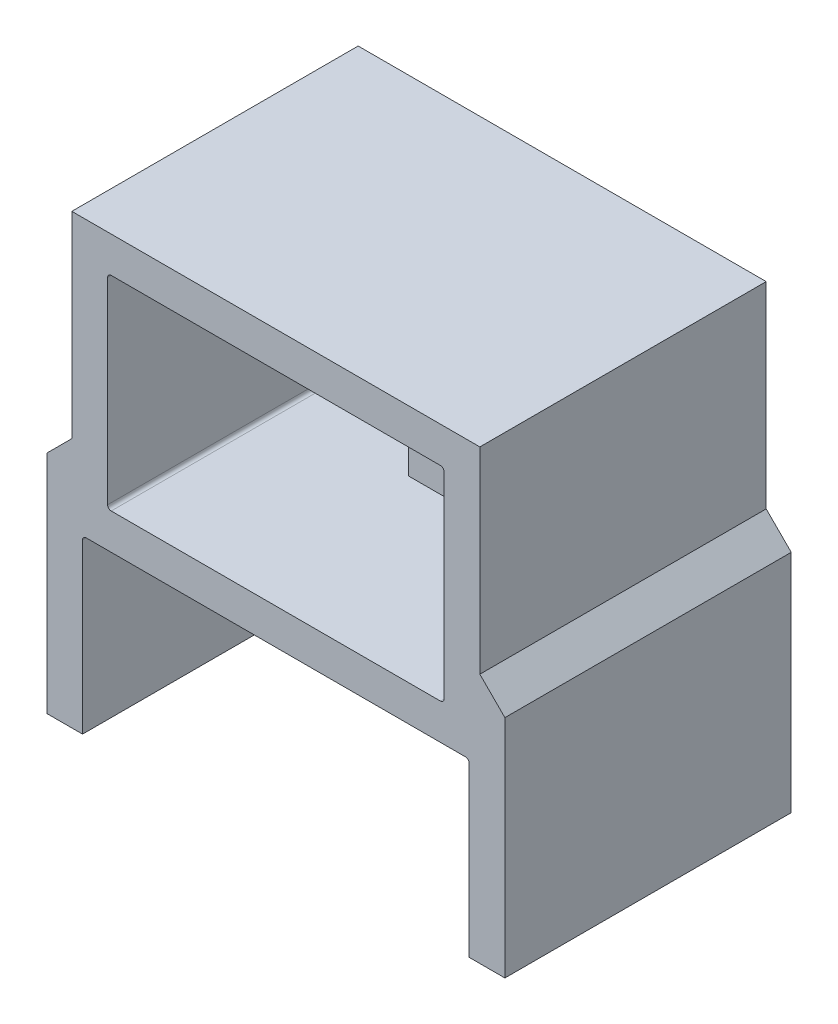
SolidWorks part; units mm, degrees
ref_plane "正面" through (0, 0, 0) normal (0, 0, 1) x (1, 0, 0)
ref_plane "平面" through (0, 0, 0) normal (0, 1, 0) x (1, 0, 0)
ref_plane "右側面" through (0, 0, 0) normal (1, 0, 0) x (0, 0, -1)
sketch "ｽｹｯﾁ1" plane through (0, 0, 0) normal (0, 0, 1) x (1, 0, 0)
  line L0 (0, 6.3) -> (0, 0)
  line L1 (0, 0) -> (12.8, 0)
  line L2 (12.8, 0) -> (12.8, 6.3)
  line L3 (12.8, 6.3) -> (12.1, 6.3)
  line L4 (12.1, 6.3) -> (12.1, 12.5)
  line L5 (12.1, 12.5) -> (0.7, 12.5)
  line L6 (0.7, 12.5) -> (0.7, 6.3)
  line L7 (0.7, 6.3) -> (0, 6.3)
  line L8 (6.4, 0) -> (6.4, -50000) construction
  point P11 (6.4, 0)
  point P12 (6.4, 12.5)
  dimension "D1" = 11.4
  dimension "D2" = 12.8
  dimension "D3" = 12.5
  dimension "D4" = 6.2
extrude "ﾎﾞｽ - 押し出し1" add sketch "ｽｹｯﾁ1" along normal blind 8
chamfer "面取り1" distance 0.7 angle 45 2 edges at (0.7, 6.3, 4) (12.1, 6.3, 4)
sketch "ｽｹｯﾁ3" plane through (0, 0, 8) normal (0, 0, 1) x (1, 0, 0)
  line L0 (12.8, 0) -> (12.8, 6.3) construction
  line L1 (1, 0) -> (11.8, 0)
  line L2 (1, 0) -> (1, 4.8)
  line L3 (1, 4.8) -> (11.8, 4.8)
  line L4 (11.8, 0) -> (11.8, 4.8)
  line L5 (0, 6.3) -> (0, 0) construction
  line L6 (12.1, 12.5) -> (0.7, 12.5) construction
  line L7 (1.7, 11.5) -> (11.1, 11.5)
  line L8 (1.7, 11.5) -> (1.7, 5.8)
  line L9 (1.7, 5.8) -> (11.1, 5.8)
  line L10 (11.1, 11.5) -> (11.1, 5.8)
  line L11 (1.7, 11.5) -> (11.1, 5.8) construction
  line L12 (1.7, 5.8) -> (11.1, 11.5) construction
  line L13 (12.1, 7) -> (12.1, 12.5) construction
  line L14 (0.7, 12.5) -> (0.7, 7) construction
  line L15 (0, 0) -> (12.8, 0) construction
  point P8 (6.4, 8.65)
  dimension "D1" = 1
  dimension "D2" = 1
  dimension "D3" = 1
  dimension "D4" = 1
  dimension "D5" = 1
  dimension "D6" = 1
  dimension "D7" = 5.7
extrude "ｶｯﾄ - 押し出し1" cut sketch "ｽｹｯﾁ3" against normal blind 7.2
fillet "ﾌｨﾚｯﾄ1" radius 0.1 6 edges at (11.8, 4.8, 4.4) (1, 4.8, 4.4) (1.7, 5.8, 4.4) (11.1, 5.8, 4.4) (11.1, 11.5, 4.4) (1.7, 11.5, 4.4)
sketch "ｽｹｯﾁ4" plane through (0, 4.8, 0) normal (0, -1, 0) x (1, 0, 0)
  line L1 (11.8, 0.8) -> (6.1, 0.8)
  line L2 (11.8, 0.8) -> (11.8, 2)
  line L3 (11.8, 2) -> (6.1, 2)
  line L4 (6.1, 0.8) -> (6.1, 2)
  dimension "D1" = 5.7
  dimension "D2" = 1.2
extrude "ｶｯﾄ - 押し出し2" cut sketch "ｽｹｯﾁ4" against normal up to surface (6.7 mm away) up to face at (6.4, 11.5, 4.4)
sketch "ｽｹｯﾁ5" plane through (0, 5.8, 0) normal (0, 1, 0) x (1, 0, 0)
  line L1 (6.6, -2) -> (10.5, -2)
  line L2 (6.6, -2) -> (6.6, -3.2)
  line L3 (6.6, -3.2) -> (10.5, -3.2)
  line L4 (10.5, -2) -> (10.5, -3.2)
  line L6 (6.1, -2) -> (6.1, -0.8) construction
  line L7 (11.7, -2) -> (6.1, -2) construction
  line L9 (11, -8) -> (11, -2) construction
  dimension "D1" = 1.2
  dimension "D2" = 0.5
  dimension "D3" = 0.5
extrude "ﾎﾞｽ - 押し出し2" add sketch "ｽｹｯﾁ5" along normal up to next
sketch "ｽｹｯﾁ6" plane through (0, 0, 0.8) normal (0, 0, 1) x (1, 0, 0)
  line L0 (4.6, 4.8) -> (4.6, 0)
  line L1 (6.1, 4.8) -> (1.1, 4.8) construction
  line L2 (1, 0) -> (11.8, 0) construction
  line L3 (4.6, 4.8) -> (6.1, 4.8)
  line L5 (6.1, 4.8) -> (6.1, 2.3)
  spline S0 degree 2 poles (6.1, 2.3) (6.0148, 0.6864) (4.6, 0) knots 0 0 0 1 1 1
  dimension "D1" = 1.5
  dimension "D2" = 1.5
  dimension "D3" = 0.5
  dimension "D4" = 2.5
extrude "ﾎﾞｽ - 押し出し3" add sketch "ｽｹｯﾁ6" along normal blind 1
sketch "ｽｹｯﾁ7" plane through (0, 5.8, 0) normal (0, 1, 0) x (1, 0, 0)
  line L1 (6.1, -2) -> (5.1, -2)
  line L2 (6.1, -2) -> (6.1, -3)
  line L3 (6.1, -3) -> (5.1, -3)
  line L4 (5.1, -2) -> (5.1, -3)
  dimension "D1" = 1
  dimension "D2" = 1
extrude "ﾎﾞｽ - 押し出し4" add sketch "ｽｹｯﾁ7" along normal up to next
